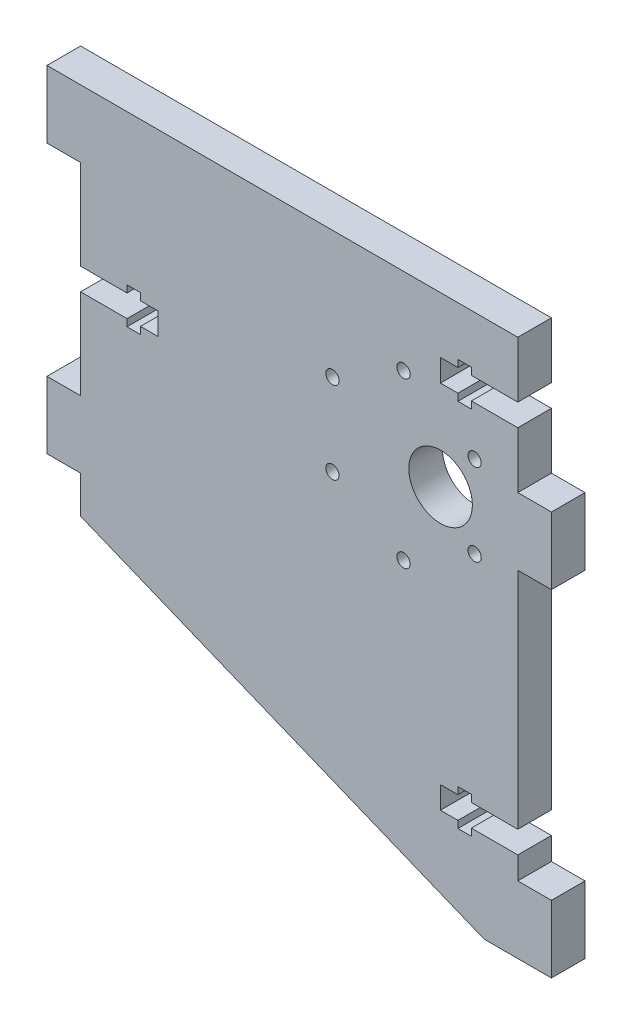
SolidWorks part; units mm, degrees
ref_plane "Front Plane" through (0, 0, 0) normal (0, 0, 1) x (1, 0, 0)
ref_plane "Top Plane" through (0, 0, 0) normal (0, 1, 0) x (1, 0, 0)
ref_plane "Right Plane" through (0, 0, 0) normal (1, 0, 0) x (0, 0, -1)
sketch "Sketch1" plane through (0, 0, 0) normal (0, 0, 1) x (1, 0, 0)
  line L0 (21.575, 33.1763) -> (21.575, -50.8) construction
  line L1 (-60.975, 31.75) -> (21.575, 31.75)
  line L2 (-60.975, 31.75) -> (-60.975, -38.7889)
  line L4 (21.575, 31.75) -> (21.575, -38.7889)
  line L5 (37.45, -38.7889) -> (-60.975, -38.7889) construction
  line L6 (-60.975, -38.7889) -> (15.225, -69.85)
  line L7 (15.225, -69.85) -> (21.575, -69.85)
  line L8 (21.575, -69.85) -> (21.575, -38.7889)
extrude "Boss-Extrude1" add sketch "Sketch1" along normal blind 6.35
sketch "Sketch2" plane through (21.575, 0, 0) normal (1, 0, 0) x (0, 0, -1)
  line L0 (0, -69.85) -> (0, 31.75) construction
  line L1 (-6.35, -69.85) -> (0, -69.85)
  line L2 (-6.35, -69.85) -> (-6.35, -57.15)
  line L3 (-6.35, -57.15) -> (0, -57.15)
  line L4 (0, -69.85) -> (0, -57.15)
  line L5 (0, -57.15) -> (-6.35, -57.15) construction
extrude "Boss-Extrude2" add sketch "Sketch2" along normal blind 6.35
pattern_linear "LPattern1" count 2 spacing 63.5 along (0, 1, 0) of "Boss-Extrude2"
sketch "Sketch3" plane through (0, 0, 0) normal (0, 0, -1) x (-1, 0, 0)
  circle A0 centre (13.4234, 7.75) radius 1.25
  circle A1 centre (13.4234, -7.75) radius 1.25
  circle A2 centre (0, 15.5) radius 1.25
  circle A3 centre (-13.4234, 7.75) radius 1.25
  circle A4 centre (-13.4234, -7.75) radius 1.25
  circle A5 centre (0, -15.5) radius 1.25
  circle A6 centre (-7, 0) radius 6
extrude "Cut-Extrude1" cut sketch "Sketch3" against normal through all
sketch "Sketch4" plane through (-60.975, 0, 0) normal (-1, 0, 0) x (0, 0, 1)
  line L0 (6.35, 31.75) -> (6.35, -38.7889) construction
  line L1 (0, 31.75) -> (6.35, 31.75)
  line L2 (0, 31.75) -> (0, 19.05)
  line L3 (0, 19.05) -> (6.35, 19.05)
  line L4 (6.35, 31.75) -> (6.35, 19.05)
  line L5 (0, 19.05) -> (6.35, 19.05) construction
  line L6 (0, 31.75) -> (0, -38.7889) construction
  line L7 (0, -19.0834) -> (6.35, -19.0834)
  line L8 (0, -19.0834) -> (0, -31.75)
  line L9 (0, -31.75) -> (6.35, -31.75)
  line L10 (6.35, -19.0834) -> (6.35, -31.75)
  line L11 (0, -31.75) -> (6.35, -31.75) construction
extrude "Boss-Extrude3" add sketch "Sketch4" along normal blind 6.35
sketch "Sketch5" plane through (0, 0, 6.35) normal (0, 0, 1) x (1, 0, 0)
  line L0 (21.575, 33.1763) -> (21.575, -50.8) construction
  line L2 (27.925, -48.7045) -> (21.575, -48.7045) construction
  line L3 (-60.975, 19.05) -> (-60.975, -19.0834) construction
  line L4 (-60.975, 2.0955) -> (-67.325, 2.0955) construction
  line L5 (21.575, 6.35) -> (21.575, 31.75) construction
  line L6 (21.575, 19.05) -> (-2.1429, 19.05) construction
  line B0 (-60.975, 2.0955) -> (-60.975, -2.0955)
  line B1 (-49.672, -2.0955) -> (-49.672, -3.429)
  line B2 (-49.672, -3.429) -> (-52.212, -3.429)
  line B3 (-52.212, -3.429) -> (-52.212, -2.0955)
  line B4 (-52.212, -2.0955) -> (-60.975, -2.0955)
  line B5 (-49.672, -2.0955) -> (-46.37, -2.0955)
  line B6 (-46.37, -2.0955) -> (-46.37, 2.0955)
  line B7 (-49.672, 2.0955) -> (-46.37, 2.0955)
  line B8 (-52.212, 2.0955) -> (-60.975, 2.0955)
  line B9 (-52.212, 3.429) -> (-52.212, 2.0955)
  line B10 (-49.672, 3.429) -> (-52.212, 3.429)
  line B11 (-49.672, 2.0955) -> (-49.672, 3.429)
  line B12 (21.575, -52.8955) -> (21.575, -48.7045)
  line B13 (10.272, -48.7045) -> (10.272, -47.371)
  line B14 (10.272, -47.371) -> (12.812, -47.371)
  line B15 (12.812, -47.371) -> (12.812, -48.7045)
  line B16 (12.812, -48.7045) -> (21.575, -48.7045)
  line B17 (10.272, -48.7045) -> (6.97, -48.7045)
  line B18 (6.97, -48.7045) -> (6.97, -52.8955)
  line B19 (10.272, -52.8955) -> (6.97, -52.8955)
  line B20 (12.812, -52.8955) -> (21.575, -52.8955)
  line B21 (12.812, -54.229) -> (12.812, -52.8955)
  line B22 (10.272, -54.229) -> (12.812, -54.229)
  line B23 (10.272, -52.8955) -> (10.272, -54.229)
  line B24 (21.575, -50.8) -> (6.97, -50.8) construction
  line B25 (21.575, 16.9545) -> (21.575, 21.1455)
  line B26 (10.272, 21.1455) -> (10.272, 22.479)
  line B27 (10.272, 22.479) -> (12.812, 22.479)
  line B28 (12.812, 22.479) -> (12.812, 21.1455)
  line B29 (12.812, 21.1455) -> (21.575, 21.1455)
  line B30 (10.272, 21.1455) -> (6.97, 21.1455)
  line B31 (6.97, 21.1455) -> (6.97, 16.9545)
  line B32 (10.272, 16.9545) -> (6.97, 16.9545)
  line B33 (12.812, 16.9545) -> (21.575, 16.9545)
  line B34 (12.812, 15.621) -> (12.812, 16.9545)
  line B35 (10.272, 15.621) -> (12.812, 15.621)
  line B36 (10.272, 16.9545) -> (10.272, 15.621)
sketch_block_instance "TSlot-1"
sketch_block "TSlot" parameters "D1"=3.302, "D2"=2.54, "D3"=3.175, "D4"=8.763, "D5"=1.3462
sketch_block_instance "TSlot-3"
sketch_block_instance "TSlot-6"
extrude "Cut-Extrude2" cut sketch "Sketch5" against normal through all
